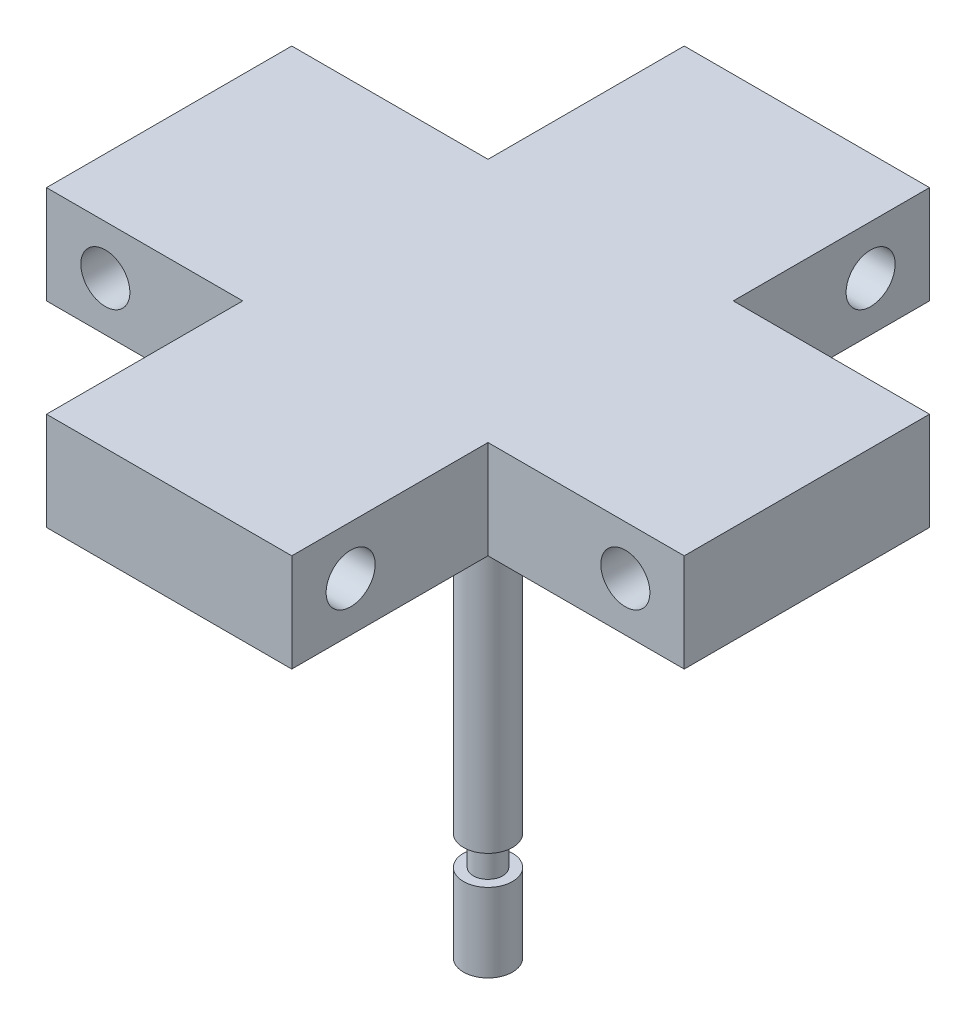
SolidWorks part; units mm, degrees
ref_plane "Front Plane" through (0, 0, 0) normal (0, 0, 1) x (1, 0, 0)
ref_plane "Top Plane" through (0, 0, 0) normal (0, 1, 0) x (1, 0, 0)
ref_plane "Right Plane" through (0, 0, 0) normal (1, 0, 0) x (0, 0, -1)
sketch "Sketch1" plane through (0, 0, 0) normal (0, 1, 0) x (1, 0, 0)
  line L1 (12.5, -12.5) -> (-12.5, -12.5)
  line L2 (12.5, -12.5) -> (12.5, 12.5)
  line L3 (12.5, 12.5) -> (-12.5, 12.5)
  line L4 (-12.5, -12.5) -> (-12.5, 12.5)
  line L5 (12.5, -12.5) -> (-12.5, 12.5) construction
  line L6 (12.5, 12.5) -> (-12.5, -12.5) construction
  line L7 (-12.5, 12.5) -> (12.5, 12.5)
  line L8 (-12.5, 12.5) -> (-12.5, 32.5)
  line L9 (-12.5, 32.5) -> (12.5, 32.5)
  line L10 (12.5, 12.5) -> (12.5, 32.5)
  line L11 (12.5, 12.5) -> (32.5, 12.5)
  line L12 (12.5, 12.5) -> (12.5, -12.5)
  line L13 (12.5, -12.5) -> (32.5, -12.5)
  line L14 (32.5, 12.5) -> (32.5, -12.5)
  line L15 (12.5, -12.5) -> (-12.5, -12.5)
  line L16 (12.5, -12.5) -> (12.5, -32.5)
  line L17 (12.5, -32.5) -> (-12.5, -32.5)
  line L18 (-12.5, -12.5) -> (-12.5, -32.5)
  line L19 (-12.5, 12.5) -> (-32.5, 12.5)
  line L20 (-12.5, 12.5) -> (-12.5, -12.5)
  line L21 (-12.5, -12.5) -> (-32.5, -12.5)
  line L22 (-32.5, 12.5) -> (-32.5, -12.5)
  point P0 (0, 0)
  dimension "D1" = 25
  dimension "D2" = 65
  dimension "D3" = 65
extrude "Boss-Extrude1" add sketch "Sketch1" along normal blind 10 contours L19 L22 L21 L4 | L1 L18 L17 L16 | L4 L1 L2 L3 | L3 L10 L9 L8 | L14 L11 L2 L13 region at (0, 0, 22.5) region at (0, 0, 0) region at (22.5, 0, 0) region at (-22.5, 0, 0) region at (0, 0, -22.5)
sketch "Sketch2" plane through (12.5, 0, 0) normal (1, 0, 0) x (0, 0, -1)
  circle A0 centre (-26.5, 5) radius 2.5
  circle A1 centre (26.5, 5) radius 2.5
extrude "Cut-Extrude1" cut sketch "Sketch2" against normal through all
sketch "Sketch3" plane through (0, 0, 12.5) normal (0, 0, 1) x (1, 0, 0)
  circle A0 centre (26.5, 5) radius 2.5 construction
  circle A1 centre (-26.5, 5) radius 2.5 construction
  circle A2 centre (26.5, 5) radius 2.5
  circle A3 centre (-26.5, 5) radius 2.5
extrude "Cut-Extrude2" cut sketch "Sketch3" against normal through all
sketch "Sketch4" plane through (0, 0, 0) normal (0, 1, 0) x (1, 0, 0)
  circle A0 centre (0, 0) radius 2.5
  dimension "D1" = 5
extrude "Boss-Extrude2" add sketch "Sketch4" against normal blind 48
sketch "Sketch5" plane through (0, 0, 0) normal (1, 0, 0) x (0, 0, -1)
  line L0 (0, 0) -> (0, -48) construction
  line L1 (-2.5, -48) -> (2.5, -48) construction
  line L2 (2.5, -37) -> (1.5, -37)
  line L4 (2.5, -48) -> (2.5, 0) construction
  line L5 (1.5, -37) -> (1.5, -40)
  line L6 (1.5, -40) -> (2.5, -40)
  line L7 (2.5, -37) -> (2.5, -40)
  dimension "D1" = 1
  dimension "D2" = 8
  dimension "D3" = 3
revolve "Cut-Revolve1" cut sketch "Sketch5" angle 360 about L0
